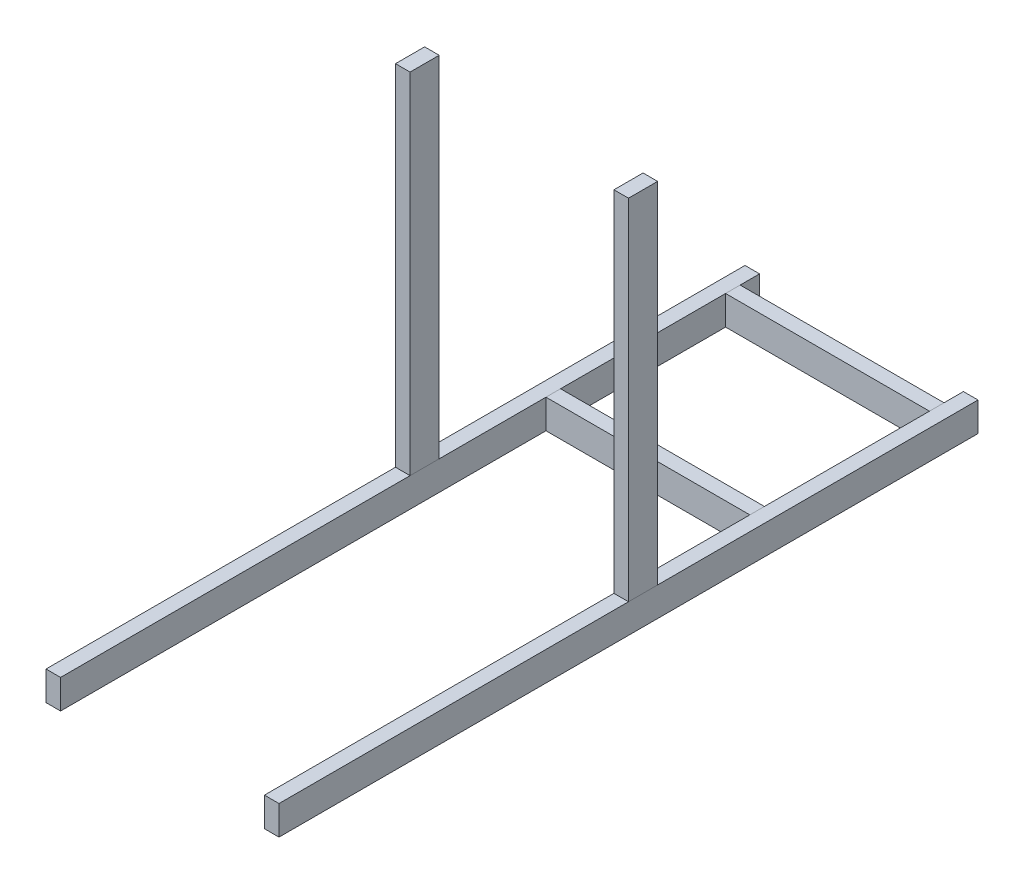
SolidWorks part; units mm, degrees
material "6061-T6 (SS)"
ref_plane "Front Plane" through (0, 0, 0) normal (0, 0, 1) x (1, 0, 0)
ref_plane "Top Plane" through (0, 0, 0) normal (0, 1, 0) x (1, 0, 0)
ref_plane "Right Plane" through (0, 0, 0) normal (1, 0, 0) x (0, 0, -1)
sketch "Sketch1" plane through (0, 0, 0) normal (0, 0, 1) x (1, 0, 0)
  line L0 (0, -90.2611) -> (0, 372.4246) construction
  line L1 (-266.7, 19.05) -> (-266.7, 95.25)
  line L2 (266.7, 19.05) -> (304.8, 19.05)
  line L3 (266.7, 19.05) -> (266.7, 95.25)
  line L4 (266.7, 95.25) -> (304.8, 95.25)
  line L5 (304.8, 19.05) -> (304.8, 95.25)
  line L6 (-266.7, 19.05) -> (-304.8, 19.05)
  line L7 (-304.8, 19.05) -> (-304.8, 95.25)
  line L8 (-266.7, 95.25) -> (-304.8, 95.25)
  point P1 (206.1502, 95.25)
  point P11 (266.7, 125.114)
  dimension "D2" = 76.2
  dimension "D1" = 533.4
  dimension "D3" = 38.1
  dimension "D4" = 19.05
extrude "Boss-Extrude1" add sketch "Sketch1" against normal blind 1828.8
sketch "Sketch2" plane through (0, 0, 0) normal (1, 0, 0) x (0, 0, -1)
  line L0 (1828.8, 19.05) -> (0, 19.05) construction
  line L1 (1778, 95.25) -> (1739.9, 95.25)
  line L2 (1778, 95.25) -> (1778, 19.05)
  line L3 (1778, 19.05) -> (1739.9, 19.05)
  line L4 (1739.9, 95.25) -> (1739.9, 19.05)
  line L5 (1308.1, 95.25) -> (1270, 95.25)
  line L6 (1308.1, 95.25) -> (1308.1, 19.05)
  line L7 (1308.1, 19.05) -> (1270, 19.05)
  line L8 (1270, 95.25) -> (1270, 19.05)
  line L10 (0, 19.05) -> (0, 95.25) construction
  point P8 (1796.9447, 171.1142)
  dimension "D1" = 38.1
  dimension "D2" = 76.2
  dimension "D4" = 38.1
  dimension "D5" = 508
  dimension "D6" = 1270
extrude "Boss-Extrude2" add sketch "Sketch2" along normal up to next (266.7 mm away) and the other way up to next (266.7 mm away) separate body
sketch "Sketch3" plane through (0, 95.25, 0) normal (0, 1, 0) x (1, 0, 0)
  line L0 (0, -1000) -> (0, 49000) construction
  line L1 (-266.7, 914.4) -> (-266.7, 990.6)
  line L2 (266.7, 914.4) -> (304.8, 914.4)
  line L3 (266.7, 914.4) -> (266.7, 990.6)
  line L4 (266.7, 990.6) -> (304.8, 990.6)
  line L5 (304.8, 914.4) -> (304.8, 990.6)
  line L6 (-266.7, 914.4) -> (-304.8, 914.4)
  line L7 (-304.8, 914.4) -> (-304.8, 990.6)
  line L8 (-266.7, 990.6) -> (-304.8, 990.6)
  line L9 (266.7, 1828.8) -> (266.7, 0) construction
  line L10 (304.8, 0) -> (266.7, 0) construction
  dimension "D1" = 38.1
  dimension "D2" = 76.2
  dimension "D3" = 914.4
extrude "Boss-Extrude3" add sketch "Sketch3" along normal blind 914.4 separate body
equation "\"W 1.5\"= 1.5"
equation "\"D1@Sketch2\"=\"W 1.5\""
equation "\"H 3\"= 3"
equation "\"D2@Sketch2\"=\"H 3\""
equation "\"D4@Sketch2\"=\"W 1.5\""
equation "\"D3@Sketch2\"=\"H 3\""
equation "\"D3@Sketch1\"=\"W 1.5\""
equation "\"D2@Sketch1\"=\"H 3\""
equation "\"D1@Sketch3\"=\"W 1.5\""
equation "\"D2@Sketch3\"=\"H 3\""
equation "\"H 1.5\"= 1.5"
